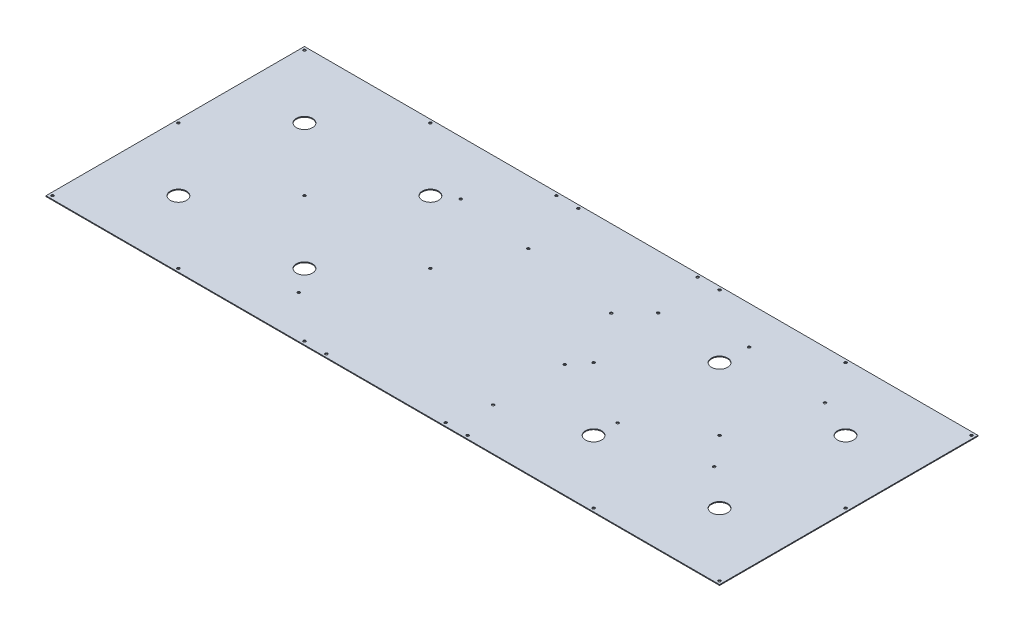
SolidWorks part; units mm, degrees
ref_plane "Front Plane" through (0, 0, 0) normal (0, 0, 1) x (1, 0, 0)
ref_plane "Top Plane" through (0, 0, 0) normal (0, 1, 0) x (1, 0, 0)
ref_plane "Right Plane" through (0, 0, 0) normal (1, 0, 0) x (0, 0, -1)
sketch "main_plate" plane through (0, 0, 0) normal (0, 1, 0) x (1, 0, 0)
  line L1 (-417, 160) -> (417, 160)
  line L2 (-417, 160) -> (-417, -160)
  line L3 (-417, -160) -> (417, -160)
  line L4 (417, 160) -> (417, -160)
  line L5 (-417, 160) -> (417, -160) construction
  line L6 (-417, -160) -> (417, 160) construction
  point P0 (0, 0)
  dimension "D1" = 320
  dimension "D2" = 834
extrude "Boss-Extrude1" add sketch "main_plate" along normal blind 1.016
sketch "main_holes" plane through (0, 1.016, 0) normal (0, 1, 0) x (1, 0, 0)
  line L0 (-417, 160) -> (-417, -160) construction
  line L1 (417, 160) -> (-417, 160) construction
  line L2 (-417, 0) -> (417, 0) construction
  line L3 (417, -160) -> (417, 160) construction
  line L4 (-417, -160) -> (417, -160) construction
  line L5 (0, 160) -> (0, -160) construction
  circle A0 centre (-413, 156) radius 1.6
  circle A6 centre (-257, 156) radius 1.6
  circle A7 centre (-101, 156) radius 1.6
  circle A8 centre (-257, 0) radius 1.6
  circle A9 centre (-101, 0) radius 1.6
  circle A10 centre (-257, -156) radius 1.6
  circle A11 centre (-101, -156) radius 1.6
  circle A12 centre (-413, 0) radius 1.6
  circle A13 centre (-413, -156) radius 1.6
  circle A18 centre (413, -156) radius 1.6
  circle A19 centre (413, 0) radius 1.6
  circle A20 centre (101, -156) radius 1.6
  circle A21 centre (257, -156) radius 1.6
  circle A22 centre (101, 0) radius 1.6
  circle A23 centre (257, 0) radius 1.6
  circle A24 centre (101, 156) radius 1.6
  circle A25 centre (257, 156) radius 1.6
  circle A28 centre (413, 156) radius 1.6
  circle A29 centre (-73.8188, 156) radius 1.6
  circle A31 centre (73.8188, 156) radius 1.6
  circle A32 centre (73.8188, -156) radius 1.6
  circle A33 centre (-73.8188, -156) radius 1.6
  dimension "D3" = 3.2
  dimension "D1" = 4
  dimension "D2" = 4
  dimension "D4" = 3
  dimension "D5" = 3
  dimension "D6" = 73.8188
extrude "Cut-Extrude1" cut sketch "main_holes" against normal through all
sketch "sma" plane through (0, 1.016, 0) normal (0, 1, 0) x (1, 0, 0)
  line L0 (0, 160) -> (0, -160) construction
  line L1 (417, 160) -> (-417, 160) construction
  line L2 (-417, -160) -> (417, -160) construction
  line L3 (-413, 156) -> (-257, 156) construction
  line L7 (-257, 0) -> (-413, 0) construction
  line L8 (-413, 0) -> (-413, 156) construction
  line L9 (-257, 156) -> (-257, 0) construction
  circle A0 centre (-335, 78) radius 10
  circle A1 centre (-179, 78) radius 10
  circle A2 centre (-179, -78) radius 10
  circle A3 centre (-335, -78) radius 10
  circle A4 centre (335, 78) radius 10
  circle A5 centre (179, 78) radius 10
  circle A6 centre (335, -78) radius 10
  circle A7 centre (179, -78) radius 10
  point P9 (-413, 78)
  point P10 (-335, 156)
  dimension "D1" = 20
  dimension "D2" = 2
  dimension "D3" = 2
extrude "Cut-Extrude2" cut sketch "sma" against normal through all
sketch "Sketch1"
  dimension "D1" = 96.5
  dimension "D2" = 112.5
  dimension "D3" = 27.8812
sketch_block_instance "Block7-3"
sketch_block "Block7" parameters "D3"=3.2, "D1"=215.9, "D2"=259.71, "D4"=6.48, "D5"=7.24, "D6"=111, "D7"=103.38, "D8"=18.04, "D9"=12.3976, "D10"=37.52, "D11"=11.13, "D12"=13.84, "D13"=110.43, "D14"=101.73, "D15"=7.74, "D16"=6.47, "D17"=37.51, "D18"=13.68, "D19"=8.76, "D20"=15.4, "D21"=8.22, "D22"=100.94, "D23"=7.02, "D24"=8.34, "D25"=18.41, "D26"=36.31, "D27"=27.78, "D28"=7.02, "D29"=8.22, "D30"=9.18, "D31"=73.31, "D32"=73.31, "D33"=82.56, "D34"=105.32, "D35"=95.85
sketch_block_instance "Block8-7"
sketch_block "Block8" parameters "D6"=3.2, "D1"=217.932, "D2"=70.358, "D3"=61.468, "D4"=193.04, "D5"=18.796, "D7"=81.28, "D8"=68.58, "D9"=94.71, "D10"=106.68, "D11"=7.2423, "D12"=10.162, "D13"=153.2296, "D14"=101.3549, "D15"=17.0315, "D16"=3.5618, "D17"=32.417, "D18"=13.2495, "D19"=3.4527, "D20"=8.4803, "D21"=3.9066, "D22"=106.752, "D23"=204.8681, "D24"=9.2076, "D25"=24.3883, "D26"=33.6172, "D27"=18.1411, "D28"=6.4986, "D29"=209.249, "D30"=9.6327, "D31"=79.4294, "D32"=79.4294, "D33"=95.4165, "D34"=105.378, "D35"=97.6492
sketch "Sketch3" plane through (0, 1.016, 0) normal (0, 1, 0) x (1, 0, 0)
  point P0 (0, 0)
  line B0 (-163.2752, -115.6705) -> (96.4348, -115.6705) construction
  line B1 (96.4348, 100.2295) -> (96.4348, -115.6705) construction
  line B2 (67.1184, 66.8966) -> (67.1184, -3.4614) construction
  line B3 (-163.2752, -115.6705) -> (96.4348, 100.2295) construction
  line B4 (85.9144, 128.1106) -> (303.8464, -64.9294) construction
  line B5 (67.1184, 31.7176) -> (303.8464, 31.5906) construction
  circle B6 centre (180.6244, 112.9368) radius 1.6
  circle B7 centre (287.3044, 100.1795) radius 1.6
  circle B8 centre (287.2308, -36.9805) radius 1.6
  circle B9 centre (180.5372, -49.6232) radius 1.6
  circle B10 centre (-156.7952, 93.2095) radius 1.6
  circle B11 centre (-149.5552, 91.8895) radius 1.6
  circle B12 centre (-155.5352, -100.2705) radius 1.6
  circle B13 centre (-156.8052, -107.4505) radius 1.6
  circle B14 centre (-14.5652, -42.3605) radius 1.6
  circle B15 centre (-6.9452, -42.3605) radius 1.6
  circle B16 centre (58.9148, -33.1105) radius 1.6
  circle B17 centre (-52.8452, -14.7305) radius 1.6
  circle B18 centre (85.3048, -19.8205) radius 1.6
  circle B19 centre (82.5948, -10.3505) radius 1.6
  circle B20 centre (78.3948, -106.4905) radius 1.6
  circle B21 centre (84.0372, -107.4505) radius 1.6
  circle B22 centre (58.9248, 63.9195) radius 1.6
  circle B23 centre (82.7548, 72.4495) radius 1.6
  circle B24 centre (87.6748, 93.2095) radius 1.6
  circle B25 centre (-61.5452, 81.8195) radius 1.6
  line B26 (85.9144, 128.1106) -> (303.8464, 128.1106) construction
  line B27 (85.9144, 128.1106) -> (85.9144, 66.8966) construction
  line B28 (85.9144, -64.9294) -> (303.8464, -64.9294) construction
  line B29 (303.8464, 128.1106) -> (303.8464, -64.9294) construction
  line B30 (85.9144, -64.9294) -> (303.8464, 128.1106) construction
  line B31 (67.1184, 66.8966) -> (85.9144, 66.8966) construction
  line B32 (67.1184, -3.4614) -> (85.9144, -3.4614) construction
  line B33 (85.9144, -64.9294) -> (85.9144, -3.4614) construction
  line B34 (-163.2752, 100.2295) -> (96.4348, 100.2295) construction
  line B35 (-163.2752, 100.2295) -> (-163.2752, -115.6705) construction
  line B36 (-163.2752, 100.2295) -> (96.4348, -115.6705) construction
sketch_block_instance "Block9-1"
sketch_block "Block9"
sketch_block_instance "Block8-8"
sketch_block_instance "Block7-4"
extrude "Cut-Extrude3" cut sketch "Sketch3" against normal through all contours B10 | B13 | B21 | B24 | B6 | B7 | B8 | B9 | B25 | B18 | B22
